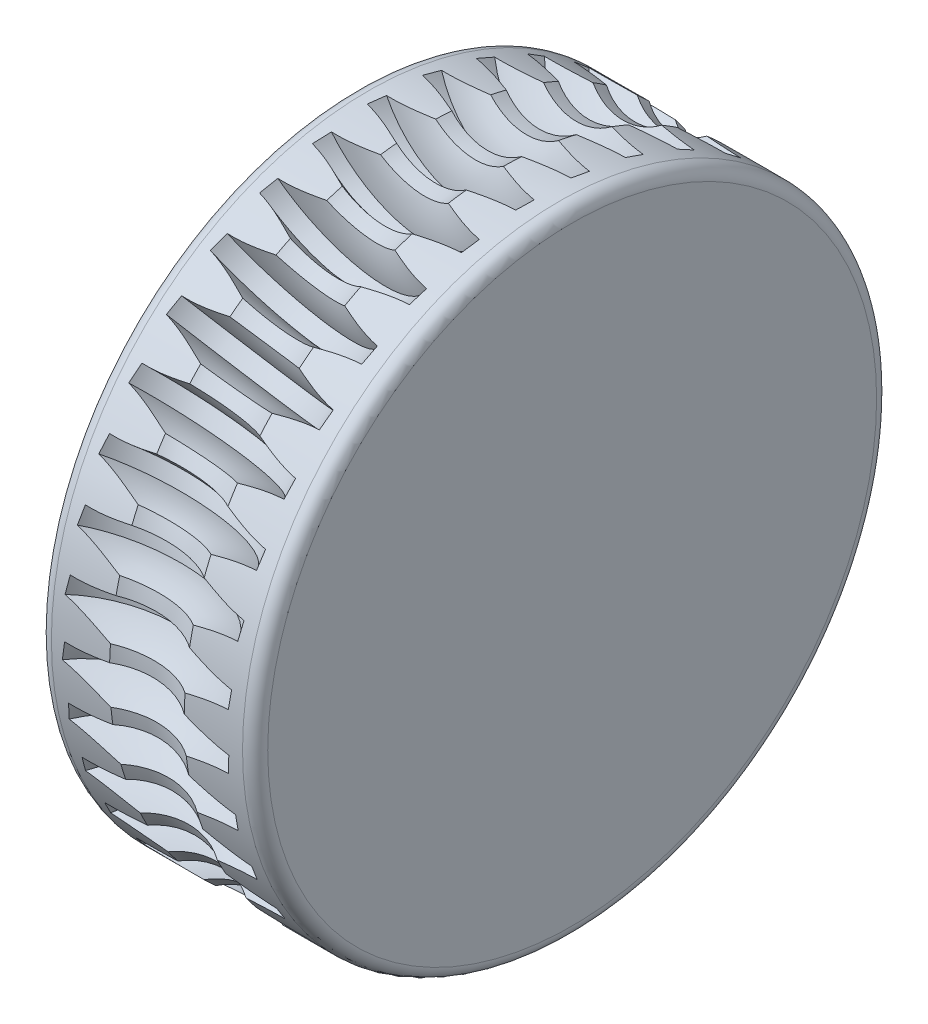
SolidWorks part; units mm, degrees
ref_plane "Front Plane" through (0, 0, 0) normal (0, 0, 1) x (1, 0, 0)
ref_plane "Top Plane" through (0, 0, 0) normal (0, 1, 0) x (1, 0, 0)
ref_plane "Right Plane" through (0, 0, 0) normal (1, 0, 0) x (0, 0, -1)
sketch "Sketch1" plane through (0, 0, 0) normal (0, 0, 1) x (1, 0, 0)
  line L0 (-6.7385, 0) -> (6.7385, 0)
  line L1 (6.7385, 0) -> (6.7385, 18.9646)
  line L2 (5.9531, 19.7501) -> (2.3319, 19.75)
  line L3 (-2.3319, 19.75) -> (-5.9531, 19.7501)
  line L4 (-6.7385, 18.9646) -> (-6.7385, 0)
  arc A1 (2.3319, 19.75) -> (-2.3319, 19.75) centre (0, 23) cw
  arc A2 (6.7385, 18.9646) -> (5.9531, 19.7501) centre (5.9531, 18.9647) ccw
  arc A3 (-5.9531, 19.7501) -> (-6.7385, 18.9646) centre (-5.9531, 18.9646) ccw
  point P3 (0, 19)
  point P4 (0, 0)
  point P12 (6.7385, 19.7501)
  dimension "D1" = 4
  dimension "D5" = 0.7854
  dimension "D2" = 13.477
  dimension "D3" = 19.7501
  dimension "D4" = 19
revolve "Revolve1" add sketch "Sketch1" angle 360 about L0
sketch "Sketch2" plane through (0, 0, 0) normal (0, 1, 0) x (1, 0, 0)
  line L0 (6.7385, 0) -> (0, 0) construction
  line L1 (6.7385, -18.9646) -> (6.7385, 18.9646) construction
  line L2 (0, 0) -> (6.7385, -0.6739) construction
  dimension "D1" = 5.711
ref_plane "Plane1" through (0, 0, 0) normal (0.995, 0, 0.0995) x (0.0995, 0, -0.995)
sketch "Sketch3" plane through (0, 0, 0) normal (0.995, 0, 0.0995) x (0.0995, 0, -0.995)
  line L0 (0, 20.5) -> (0, 0) construction
  line L1 (0, 0) -> (5.9568, 16.3662) construction
  line L2 (5.9568, 16.3662) -> (0, 18) construction
  line L3 (-0.7854, 17.9829) -> (0, 0) construction
  line L4 (-14.5908, 22.817) -> (14.5346, 22.817) construction
  arc A0 (1.3288, 20.4569) -> (-3.1072, 20.2632) centre (0, 0) ccw
  circle A1 centre (0, 0) radius 18 construction
  circle A2 centre (0, 0) radius 17.4165 construction
  arc A3 (-0.2024, 16.8318) -> (-1.2658, 16.7853) centre (0, 0) ccw
  arc A4 (1.3288, 20.4569) -> (-0.2024, 16.8318) centre (5.9568, 16.3662) ccw
  arc A5 (-3.1072, 20.2632) -> (-1.2658, 16.7853) centre (-7.361, 15.7845) cw
  point P15 (-0.7345, 16.817)
  dimension "D1" = 41
  dimension "D2" = 36
  dimension "D3" = 34.833
  dimension "D4" = 33.666
  dimension "D5" = 20
  dimension "D6" = 0.7854
  dimension "D7" = 6
revolve "Cut-Revolve1" cut sketch "Sketch3" angle 360 about L4
pattern_circular "CirPattern1" count 36 over 360 about axis through (6.7385, 0, 0) along (1, 0, 0) of "Cut-Revolve1"
